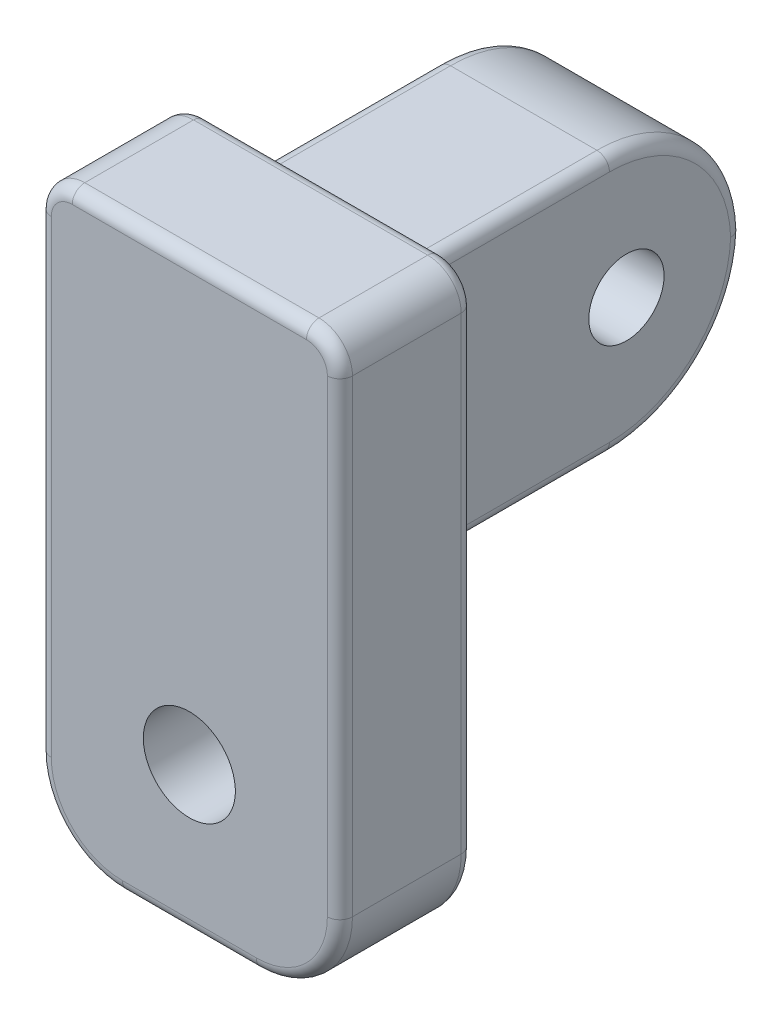
SolidWorks part; units mm, degrees
ref_plane "Front Plane" through (0, 0, 0) normal (0, 0, 1) x (1, 0, 0)
ref_plane "Top Plane" through (0, 0, 0) normal (0, 1, 0) x (1, 0, 0)
ref_plane "Right Plane" through (0, 0, 0) normal (1, 0, 0) x (0, 0, -1)
sketch "Sketch1" plane through (0, 0, 0) normal (0, 0, 1) x (1, 0, 0)
  line L1 (-9, 17.5) -> (9, 17.5)
  line L2 (-9, 17.5) -> (-9, -17.5)
  line L3 (-9, -17.5) -> (9, -17.5)
  line L4 (9, 17.5) -> (9, -17.5)
  line L5 (-9, 17.5) -> (9, -17.5) construction
  line L6 (-9, -17.5) -> (9, 17.5) construction
  point P0 (0, 0)
  dimension "D1" = 18
  dimension "D2" = 35
extrude "Boss-Extrude1" add sketch "Sketch1" along normal blind 8
sketch "Sketch2" plane through (0, 0, 0) normal (1, 0, 0) x (0, 0, -1)
  line L0 (13, 7.5) -> (20, 7.5) construction
  line L1 (0, 17.5) -> (20, 17.5)
  line L2 (0, 17.5) -> (0, -2.5)
  line L3 (0, -2.5) -> (20, -2.5)
  line L4 (20, 17.5) -> (20, -2.5)
  line L5 (0, 17.5) -> (20, -2.5) construction
  line L6 (0, -2.5) -> (20, 17.5) construction
  line L10 (0, -17.5) -> (0, 17.5)
  line L11 (0, 17.5) -> (-8, 17.5)
  line L12 (-8, 17.5) -> (-8, -17.5)
  line L13 (-8, -17.5) -> (0, -17.5)
  line L14 (0, -17.5) -> (0, 17.5) construction
  line L15 (0, 17.5) -> (-8, 17.5) construction
  line L16 (-8, 17.5) -> (-8, -17.5) construction
  line L17 (-8, -17.5) -> (0, -17.5) construction
  circle A0 centre (13, 7.5) radius 2.25
  dimension "D4" = 4.5
  dimension "D1" = 20
  dimension "D2" = 20
  dimension "D5" = 7
  dimension "D3" = 0
extrude "Boss-Extrude2" add sketch "Sketch2" along normal mid plane 10.25
fillet "Fillet1" radius 10 2 edges at (0, 17.5, -20) (0, -2.5, -20)
fillet "Fillet5" radius 5 2 edges at (9, -17.5, 4) (-9, -17.5, 4)
fillet "Fillet6" radius 2 2 edges at (-9, 17.5, 4) (9, 17.5, 4)
sketch "Sketch5" plane through (0, 0, 0) normal (0, 0, -1) x (-1, 0, 0)
  line L0 (0, 0) -> (0, -17.5) construction
  circle A0 centre (0, -8.75) radius 2.75
  circle A1 centre (0, -8.75) radius 5
  dimension "D1" = 5.5
  dimension "D3" = 10
  dimension "D2" = 17.5
extrude "Cut-Extrude1" cut sketch "Sketch5" against normal through all contours A0
extrude "Cut-Extrude2" cut sketch "Sketch5<3>" against normal blind 3
sketch "Sketch5<3>" plane through (0, 0, 0) normal (0, 0, -1) x (-1, 0, 0) same geometry as "Sketch5"
sketch "Sketch6" plane through (5.125, 0, 0) normal (1, 0, 0) x (0, 0, -1)
  line L0 (13, 7.5) -> (0, 7.5) construction
  line L1 (0, 17.5) -> (20, 17.5)
  line L2 (0, 17.5) -> (0, 15.25)
  line L3 (0, 15.25) -> (20, 15.25)
  line L4 (20, 17.5) -> (20, 15.25)
  line L5 (0, 17.5) -> (0, -2.5) construction
  line L6 (20, -2.5) -> (20, -0.25)
  line L7 (0, -0.25) -> (20, -0.25)
  line L8 (0, -2.5) -> (0, -0.25)
  line L9 (0, -2.5) -> (20, -2.5)
  dimension "D1" = 2.25
extrude "Cut-Extrude3" cut sketch "Sketch6" against normal through all
fillet "Fillet8" radius 8 2 edges at (0, -0.25, -16.3196) (0, 15.25, -16.3196)
fillet "Fillet11" radius 0.75 28 edges at (-5.125, 7.5, 0) (0, -0.25, 0) (0, 15.25, 0) (7.5355, -16.0355, 8) (0, -17.5, 8) (-7.5355, -16.0355, 8) (-9, 1.5, 8) (-8.4142, 16.9142, 8) (0, 17.5, 8) (8.4142, 16.9142, 8) (7.5355, -16.0355, 0) (0, -17.5, 0) (-7.5355, -16.0355, 0) (-9, 1.5, 0) (-8.4142, 16.9142, 0) (0, 17.5, 0) (8.4142, 16.9142, 0) (5.125, -0.25, -5.9922) (-5.125, -0.25, -5.9922) (9, 1.5, 8) (9, 1.5, 0) (5.125, 7.5, 0) (5.125, 2.0054, -17.5521) (5.125, 15.25, -5.9922) (5.125, 12.9946, -17.5521) (-5.125, 2.0054, -17.5521) (-5.125, 15.25, -5.9922) (-5.125, 12.9946, -17.5521)
